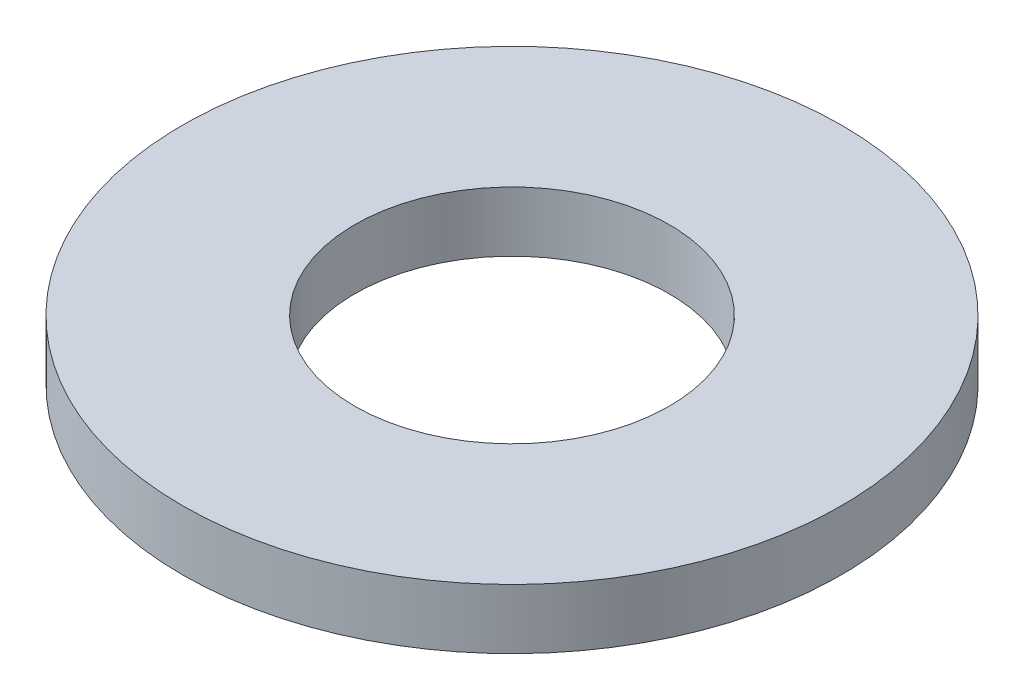
SolidWorks part; units mm, degrees
material "ACIER EZ"
ref_plane "Front Plane" through (0, 0, 0) normal (0, 0, 1) x (1, 0, 0)
ref_plane "Top Plane" through (0, 0, 0) normal (0, 1, 0) x (1, 0, 0)
ref_plane "Right Plane" through (0, 0, 0) normal (1, 0, 0) x (0, 0, -1)
sketch "Sketch1" plane through (0, 0, 0) normal (0, 1, 0) x (1, 0, 0)
  circle A0 centre (0, 0) radius 11
  circle A1 centre (0, 0) radius 5.25
  dimension "D1" = 22
  dimension "D2" = 10.5
sheet metal parameters "Sheet-Metal1" thickness 2 parameters "D1"=0.6, "Epaisseur"=2
base flange "Base-Flange1" sketch "Sketch1" thickness 2 reverse thickness direction no parameters "D1"=0.6
flat pattern "Flat-Pattern1" [suppressed]
sketch "Sketch3" plane through (0, 0, 0) normal (0, 1, 0) x (1, 0, 0)
sketch "Sketch5" [suppressed] plane through (0, 0, 0) normal (0, 1, 0) x (1, 0, 0)
